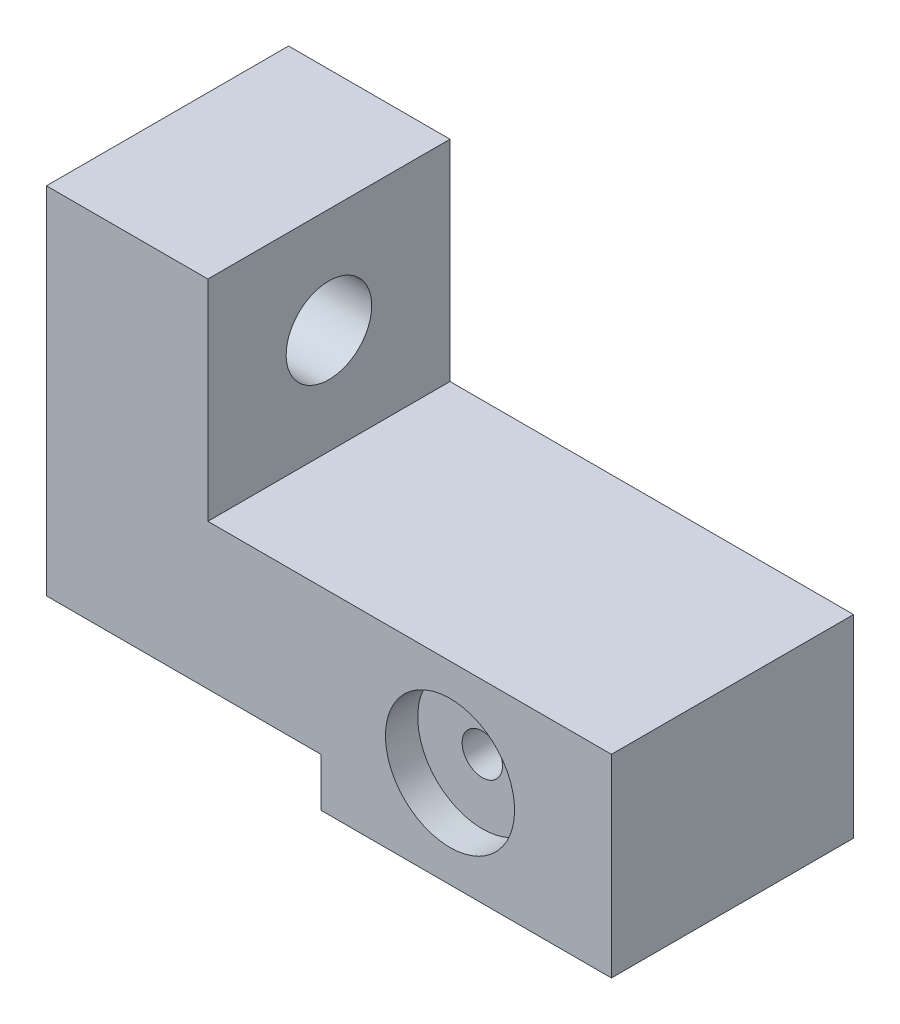
SolidWorks part; units mm, degrees
ref_plane "Front Plane" through (0, 0, 0) normal (0, 0, 1) x (1, 0, 0)
ref_plane "Top Plane" through (0, 0, 0) normal (0, 1, 0) x (1, 0, 0)
ref_plane "Right Plane" through (0, 0, 0) normal (1, 0, 0) x (0, 0, -1)
sketch "Sketch1" plane through (0, 0, 0) normal (0, 0, 1) x (1, 0, 0)
  line L0 (35, 0) -> (17, 0)
  line L1 (35, 0) -> (35, 12)
  line L2 (35, 12) -> (10, 12)
  line L3 (10, 12) -> (10, 25)
  line L4 (10, 25) -> (0, 25)
  line L5 (0, 25) -> (0, 3)
  line L6 (17, 0) -> (17, 3)
  line L7 (17, 3) -> (0, 3)
  dimension "D2" = 12
  dimension "D3" = 10
  dimension "D4" = 13
  dimension "D5" = 9
  dimension "D6" = 17
extrude "Boss-Extrude1" add sketch "Sketch1" along normal blind 15
sketch "Sketch3" plane through (10, 0, 0) normal (1, 0, 0) x (0, 0, -1)
  line L0 (-7.5, 25) -> (-7.5, 12) construction
  line L1 (-15, 25) -> (0, 25) construction
  line L2 (-15, 12) -> (0, 12) construction
  line L3 (0, 18.5) -> (-15, 18.5) construction
  line L4 (0, 12) -> (0, 25) construction
  line L5 (-15, 12) -> (-15, 25) construction
  circle A0 centre (-7.5, 18.5) radius 2.65
  dimension "D1" = 5.3
extrude "Cut-Extrude1" cut sketch "Sketch3" against normal blind 15
sketch "Sketch4" plane through (0, 0, 15) normal (0, 0, 1) x (1, 0, 0)
  line L0 (35, 6) -> (0, 6) construction
  line L1 (35, 0) -> (35, 12) construction
  point P6 (25, 6)
  dimension "D1" = 10
hole_wizard "M3 Tapped Hole1" positions "3DSketch1" profile "Sketch6" tap size "M3" standard "DIN" end condition through all
sketch3d "3DSketch1"
  point P0 (25, 6, 15)
sketch "Sketch6" plane through (25, 6, 15) normal (1, 0, 0) x (0, -1, 0)
  line L0 (0, 0) -> (0, 15)
  line L1 (0, 15) -> (1.25, 15)
  line L2 (1.25, 15) -> (1.25, 0)
  line L5 (1.25, 0) -> (0, 0)
  line L11 (0, -6.35) -> (0, 107.95) construction
  dimension "Thru Tap Drill Dia." = 2.5
  dimension "Thru Tap Drill Depth" = 15
cosmetic thread "Hole Thread1" parameters "D2"=3
sketch "Sketch7" plane through (0, 0, 15) normal (0, 0, 1) x (1, 0, 0)
  circle A0 centre (25, 6) radius 4
  dimension "D1" = 8
extrude "Cut-Extrude2" cut sketch "Sketch7" against normal blind 2
